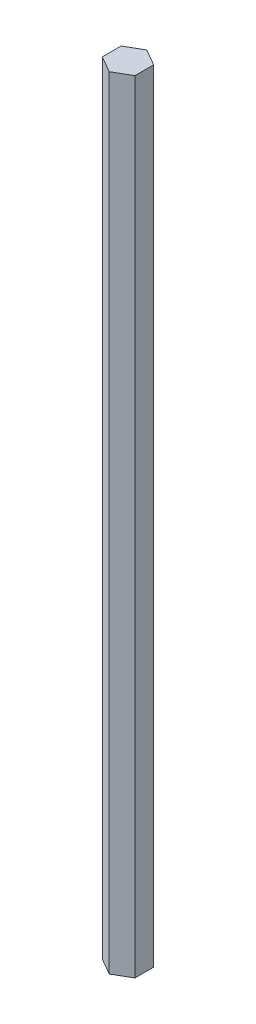
SolidWorks part; units mm, degrees
ref_plane "Front Plane" through (0, 0, 0) normal (0, 0, 1) x (1, 0, 0)
ref_plane "Top Plane" through (0, 0, 0) normal (0, 1, 0) x (1, 0, 0)
ref_plane "Right Plane" through (0, 0, 0) normal (1, 0, 0) x (0, 0, -1)
sketch "Sketch1" plane through (0, 0, 0) normal (0, 1, 0) x (1, 0, 0)
  line L1 (6.3495, -3.6671) -> (6.3505, 3.6653)
  line L2 (6.3505, 3.6653) -> (0.0011, 7.3323)
  line L3 (0.0011, 7.3323) -> (-6.3495, 3.6671)
  line L4 (-6.3495, 3.6671) -> (-6.3505, -3.6653)
  line L5 (-6.3505, -3.6653) -> (-0.0011, -7.3323)
  line L6 (-0.0011, -7.3323) -> (6.3495, -3.6671)
  circle A1 centre (0, 0) radius 6.35 construction
extrude "Boss-Extrude1" add sketch "Sketch1" along normal mid plane 304.8
